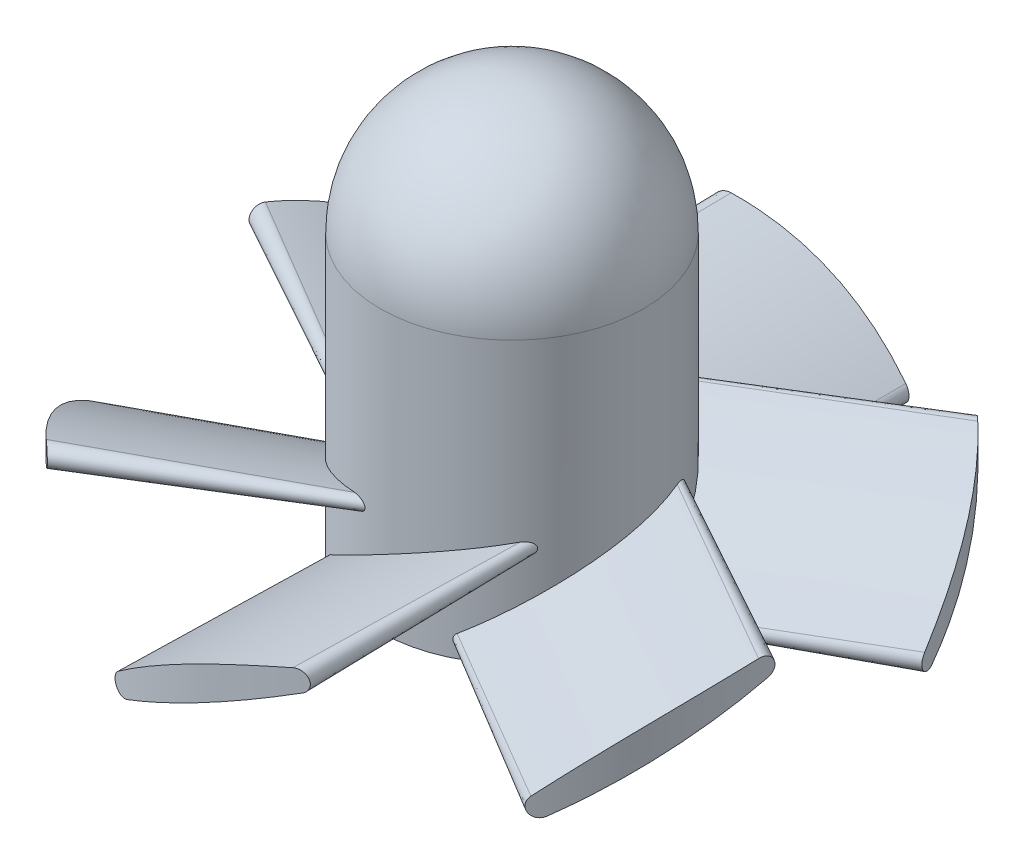
SolidWorks part; units mm, degrees
ref_plane "Plan de face" through (0, 0, 0) normal (0, 0, 1) x (1, 0, 0)
ref_plane "Plan de dessus" through (0, 0, 0) normal (0, 1, 0) x (1, 0, 0)
ref_plane "Plan de droite" through (0, 0, 0) normal (1, 0, 0) x (0, 0, -1)
sketch "Esquisse1" plane through (0, 0, 0) normal (0, 0, 1) x (1, 0, 0)
  line L0 (0, 34.9949) -> (0, -7.8007) construction
  line L1 (0, 0) -> (8, 0)
  line L2 (8, 0) -> (8, 17)
  line L3 (0, 25) -> (0, 0)
  arc A0 (8, 17) -> (0, 25) centre (0, 17) ccw
  dimension "D1" = 16
  dimension "D2" = 25
revolve "Révolution1" add sketch "Esquisse1" angle 360 about L0
sketch "Esquisse2" plane through (0, 0, 0) normal (0, 0, 1) x (1, 0, 0)
  line L0 (-3.8658, 0.7317) -> (6.1342, 5.7317)
  arc A0 (-4.1823, 1.2383) -> (5.9187, 6.2888) centre (14.0448, -22.5897) cw
  arc A2 (5.9187, 6.2888) -> (6.1342, 5.7317) centre (6, 6) cw
  arc A3 (-3.8658, 0.7317) -> (-4.1823, 1.2383) centre (-4, 1) cw
  point P6 (0, 0)
  dimension "D4" = 30
  dimension "D6" = 0.3
  dimension "D1" = 1
  dimension "D2" = 5
  dimension "D3" = 4
  dimension "D5" = 10
extrude "Boss.-Extru.1" add sketch "Esquisse2" along normal blind 30 draft 1 draft outward yes
ref_axis "Axe1" through (0, 26.2674, 0) along (0, -1, 0)
pattern_circular "Répétition circulaire1" count 6 over 360 about axis through (0, 26.2674, 0) along (0, -1, 0) of "Boss.-Extru.1"
sketch "Esquisse3" plane through (0, 0, 0) normal (0, 1, 0) x (1, 0, 0)
  circle A0 centre (0, 0) radius 20
  dimension "D1" = 40
extrude "Enlèv. mat.-Extru.1" cut sketch "Esquisse3" along normal through all flip side to cut
